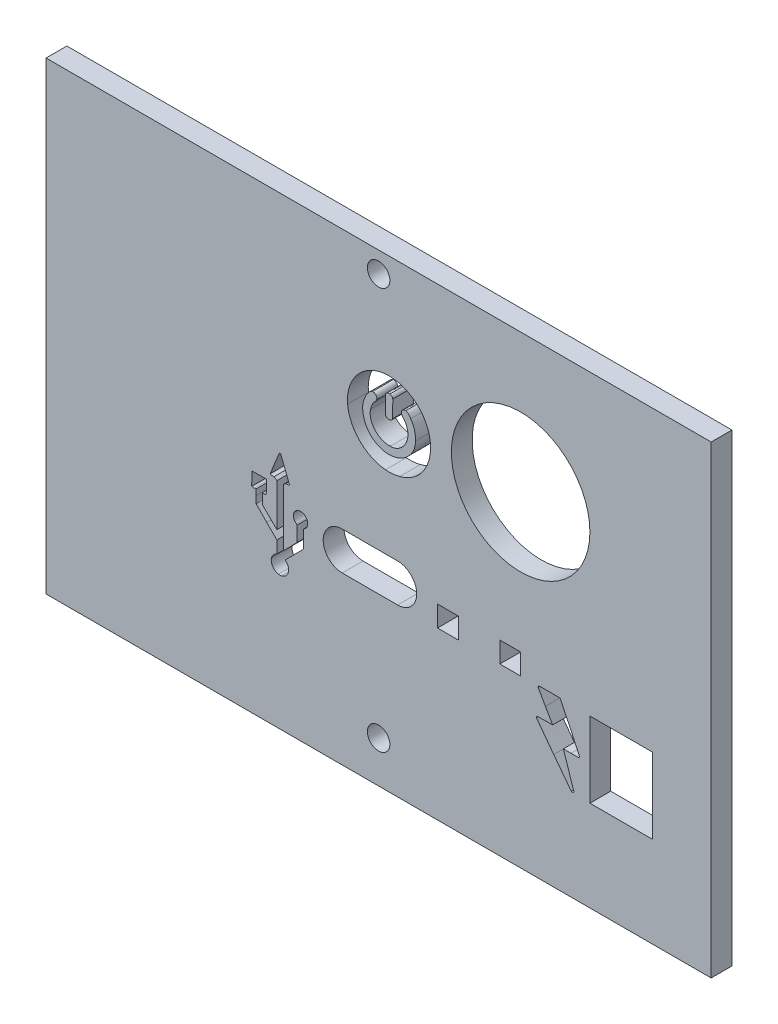
SolidWorks part; units mm, degrees
ref_plane "Alzado" through (0, 0, 0) normal (0, 0, 1) x (1, 0, 0)
ref_plane "Planta" through (0, 0, 0) normal (0, 1, 0) x (1, 0, 0)
ref_plane "Vista lateral" through (0, 0, 0) normal (1, 0, 0) x (0, 0, -1)
sketch "Croquis6" plane through (0, 0, 0) normal (0, 0, 1) x (1, 0, 0)
  line L1 (-48, -33.5) -> (48, -33.5)
  line L2 (-48, -33.5) -> (-48, 33.5)
  line L3 (-48, 33.5) -> (48, 33.5)
  line L4 (48, -33.5) -> (48, 33.5)
  line L5 (-48, -33.5) -> (48, 33.5) construction
  line L6 (-48, 33.5) -> (48, -33.5) construction
  point P0 (0, 0)
  dimension "D1" = 96
  dimension "D2" = 67
extrude "Saliente-Extruir1" add sketch "Croquis6" along normal blind 3
sketch "Croquis7" plane through (0, 0, 0) normal (0, 0, 1) x (1, 0, 0)
  line L5 (48, 33.5) -> (-48, 33.5) construction
  line L13 (-48, -33.5) -> (48, -33.5) construction
  line L14 (30.5, -9.5) -> (39.5, -9.5)
  line L15 (30.5, -9.5) -> (30.5, -20.4)
  line L16 (30.5, -20.4) -> (39.5, -20.4)
  line L17 (39.5, -9.5) -> (39.5, -20.4)
  line L18 (30.5, -9.5) -> (39.5, -20.4) construction
  line L19 (30.5, -20.4) -> (39.5, -9.5) construction
  line L20 (-48, 33.5) -> (-48, -33.5) construction
  line L21 (2.75, -6.75) -> (-5.25, -6.75) construction
  line L22 (2.75, -9.5) -> (-5.25, -9.5)
  line L23 (2.75, -4) -> (-5.25, -4)
  line L24 (48, -33.5) -> (48, 33.5) construction
  line L25 (8.5, -9.5) -> (11.5, -9.5)
  line L26 (8.5, -9.5) -> (8.5, -6.5)
  line L27 (8.5, -6.5) -> (11.5, -6.5)
  line L28 (11.5, -9.5) -> (11.5, -6.5)
  line L29 (8.5, -9.5) -> (11.5, -6.5) construction
  line L30 (8.5, -6.5) -> (11.5, -9.5) construction
  line L32 (17.5, -9.5) -> (20.5, -9.5)
  line L33 (17.5, -9.5) -> (17.5, -6.5)
  line L34 (17.5, -6.5) -> (20.5, -6.5)
  line L35 (20.5, -9.5) -> (20.5, -6.5)
  line L36 (17.5, -9.5) -> (20.5, -6.5) construction
  line L37 (17.5, -6.5) -> (20.5, -9.5) construction
  arc A0 (2.75, -9.5) -> (2.75, -4) centre (2.75, -6.75) ccw
  arc A1 (-5.25, -4) -> (-5.25, -9.5) centre (-5.25, -6.75) ccw
  circle A2 centre (0, -27.5) radius 1.625 construction
  circle A4 centre (0, -27.5) radius 1.625
  circle A5 centre (0, 30.5) radius 1.625
  circle A6 centre (20.5, 13.5) radius 10
  point P12 (35, -14.95)
  point P23 (-1.25, -6.75)
  point P34 (10, -8)
  point P41 (19, -8)
  dimension "D11" = 42.75
  dimension "D12" = 39.5
  dimension "D2" = 20
  dimension "D3" = 27.5
  dimension "D4" = 20
  dimension "D16" = 3.25
  dimension "D17" = 3
  dimension "D18" = 48
  dimension "D5" = 10.9
  dimension "D6" = 9
  dimension "D7" = 24
  dimension "D8" = 87.5
  dimension "D9" = 8
  dimension "D10" = 5.5
  dimension ".5" = 29.5
  dimension "D13" = 24
  dimension "D14" = 3
  dimension "D15" = 6
extrude "Cortar-Extruir1" cut sketch "Croquis7" along normal through all
sketch "Sketch3" plane through (0, 0, 0) normal (0, 0, -1) x (-1, 0, 0)
  line L0 (13.3471, -12.1213) -> (13.4863, -11.9807)
  line L1 (13.4863, -11.9807) -> (12.1786, -10.6698)
  line L2 (10.8062, -7.9977) -> (10.8062, -6.7645)
  line L3 (10.8062, -6.7645) -> (10.695, -6.6943)
  line L4 (11.8656, -6.6758) -> (11.7461, -6.7491)
  line L5 (11.7461, -6.7491) -> (11.7462, -7.8341)
  line L6 (11.7462, -7.8341) -> (11.7463, -8.9191)
  line L7 (11.7463, -8.9191) -> (12.7195, -9.9308)
  line L8 (13.7386, -6.8102) -> (13.7386, -2.6584)
  line L9 (13.7386, -2.6584) -> (13.366, -2.3916)
  line L10 (15.1031, -2.3917) -> (14.6769, -2.6585)
  line L11 (14.6769, -2.6585) -> (14.6769, -5.7252)
  line L12 (14.6769, -5.7252) -> (14.6769, -8.7919)
  line L13 (14.6769, -8.7919) -> (15.7326, -7.7564)
  line L14 (15.7326, -7.7564) -> (16.7882, -6.7209)
  line L15 (16.7882, -6.7209) -> (16.7882, -5.9799)
  line L16 (16.7882, -5.9799) -> (16.7882, -5.239)
  line L17 (16.7882, -5.239) -> (16.5517, -5.239)
  line L18 (16.2018, -4.2113) -> (16.2018, -3.2442)
  line L19 (16.2018, -3.2442) -> (17.2501, -3.2522)
  line L20 (17.2501, -3.2522) -> (18.2984, -3.2602)
  line L21 (18.2984, -3.2602) -> (18.3064, -4.2211)
  line L22 (18.3064, -4.2211) -> (18.3144, -5.1821)
  line L23 (18.3144, -5.1821) -> (18.2388, -5.2108)
  line L24 (17.9452, -5.2395) -> (17.7272, -5.2395)
  line L25 (17.7272, -5.2395) -> (17.7272, -6.0908)
  line L26 (16.1572, -8.6206) -> (14.6775, -10.0831)
  line L27 (14.6775, -10.0831) -> (14.6775, -10.9544)
  line L28 (14.6775, -10.9544) -> (14.6775, -11.8257)
  line L29 (14.6775, -11.8257) -> (14.8112, -11.8907)
  line L30 (14.0062, -14.2401) -> (14.0057, -14.239)
  spline S0 degree 3 poles (14.0057, -14.239) (13.7865, -14.196) (13.5245, -14.0539) (13.3588, -13.8881) knots 0 0 0 0 1 1 1 1
  spline S1 degree 3 poles (13.3588, -13.8881) (12.8723, -13.4016) (12.867, -12.6065) (13.3471, -12.1213) knots 0 0 0 0 1 1 1 1
  spline S2 degree 3 poles (12.1786, -10.6698) (11.4594, -9.9488) (10.8564, -9.3301) (10.8386, -9.2949) knots 0 0 0 0 1 1 1 1
  spline S3 degree 3 poles (10.8386, -9.2949) (10.8165, -9.2512) (10.8062, -8.8393) (10.8062, -7.9977) knots 0 0 0 0 1 1 1 1
  spline S4 degree 3 poles (10.695, -6.6943) (10.4182, -6.5196) (10.238, -6.1959) (10.2359, -5.8694) knots 0 0 0 0 1 1 1 1
  spline S5 degree 3 poles (10.2359, -5.8694) (10.2339, -5.6076) (10.2834, -5.4406) (10.4211, -5.2407) knots 0 0 0 0 1 1 1 1
  spline S6 degree 3 poles (10.4211, -5.2407) (10.849, -4.6193) (11.784, -4.668) (12.1635, -5.3314) knots 0 0 0 0 1 1 1 1
  spline S7 degree 3 poles (12.1635, -5.3314) (12.4235, -5.7858) (12.283, -6.4198) (11.8656, -6.6758) knots 0 0 0 0 1 1 1 1
  spline S8 degree 3 poles (12.7195, -9.9308) (13.2548, -10.4872) (13.7031, -10.9468) (13.7157, -10.9522) knots 0 0 0 0 1 1 1 1
  spline S9 degree 3 poles (13.7157, -10.9522) (13.7283, -10.9572) (13.7386, -9.0937) (13.7386, -6.8102) knots 0 0 0 0 1 1 1 1
  spline S10 degree 3 poles (13.366, -2.3916) (12.9578, -2.3916) (12.8839, -2.3687) (12.8839, -2.2422) knots 0 0 0 0 1 1 1 1
  spline S11 degree 3 poles (12.8839, -2.2422) (12.8839, -2.2029) (13.1643, -1.478) (13.5069, -0.6316) knots 0 0 0 0 1 1 1 1
  spline S12 degree 3 poles (13.5069, -0.6316) (13.8496, 0.2148) (14.1361, 0.9233) (14.1438, 0.9428) knots 0 0 0 0 1 1 1 1
  spline S13 degree 3 poles (14.1438, 0.9428) (14.1658, 0.9995) (14.2718, 1.0203) (14.3144, 0.9762) knots 0 0 0 0 1 1 1 1
  spline S14 degree 3 poles (14.3144, 0.9762) (14.3631, 0.9259) (15.6184, -2.1776) (15.6184, -2.2476) knots 0 0 0 0 1 1 1 1
  spline S15 degree 3 poles (15.6184, -2.2476) (15.6184, -2.3723) (15.5491, -2.3917) (15.1031, -2.3917) knots 0 0 0 0 1 1 1 1
  spline S16 degree 3 poles (16.5517, -5.239) (16.1693, -5.239) (16.2018, -5.3343) (16.2018, -4.2113) knots 0 0 0 0 1 1 1 1
  spline S17 degree 3 poles (18.2388, -5.2108) (18.1972, -5.2266) (18.0651, -5.2395) (17.9452, -5.2395) knots 0 0 0 0 1 1 1 1
  spline S18 degree 3 poles (17.7272, -6.0908) (17.7272, -6.7908) (17.7192, -6.9614) (17.6821, -7.0501) knots 0 0 0 0 1 1 1 1
  spline S19 degree 3 poles (17.6821, -7.0501) (17.6511, -7.1245) (17.1757, -7.614) (16.1572, -8.6206) knots 0 0 0 0 1 1 1 1
  spline S20 degree 3 poles (14.8112, -11.8907) (15.0985, -12.0302) (15.3701, -12.3691) (15.4573, -12.6967) knots 0 0 0 0 1 1 1 1
  spline S21 degree 3 poles (15.4573, -12.6967) (15.641, -13.3866) (15.1812, -14.1075) (14.4716, -14.2421) knots 0 0 0 0 1 1 1 1
  spline S22 degree 3 poles (14.4716, -14.2421) (14.2944, -14.2757) (14.1872, -14.2751) (14.0062, -14.2401) knots 0 0 0 0 1 1 1 1
sketch "Sketch4" plane through (0, 0, 0) normal (0, 0, -1) x (-1, 0, 0)
  line L0 (-27.7842, -15.5148) -> (-28.9122, -15.5148)
  line L1 (-28.9122, -15.5148) -> (-28.9564, -15.4586)
  spline S0 degree 3 poles (-28.3132, -15.5201) (-28.0114, -15.5168) (-27.5175, -15.5168) (-27.2156, -15.5201) knots 0 0 0 0 1 1 1 1
  spline S1 degree 3 poles (-27.2156, -15.5201) (-26.9138, -15.5235) (-27.1607, -15.5262) (-27.7644, -15.5262) knots 0 0 0 0 1 1 1 1
  spline S2 degree 3 poles (-27.7644, -15.5262) (-28.3681, -15.5262) (-28.6151, -15.5235) (-28.3132, -15.5201) knots 0 0 0 0 1 1 1 1
  spline S3 degree 3 poles (-24.5927, -13.3036) (-24.2959, -13.3003) (-23.8164, -13.3003) (-23.5271, -13.3036) knots 0 0 0 0 1 1 1 1
  spline S4 degree 3 poles (-23.5271, -13.3036) (-23.2378, -13.307) (-23.4806, -13.3097) (-24.0667, -13.3097) knots 0 0 0 0 1 1 1 1
  spline S5 degree 3 poles (-24.0667, -13.3097) (-24.6528, -13.3097) (-24.8895, -13.307) (-24.5927, -13.3036) knots 0 0 0 0 1 1 1 1
  spline S6 degree 3 poles (-28.0521, -20.2906) (-28.1292, -20.2578) (-28.1791, -20.1828) (-28.1784, -20.1006) knots 0 0 0 0 1 1 1 1
  spline S7 degree 3 poles (-28.1784, -20.1006) (-28.1781, -20.0552) (-27.8583, -19.0806) (-27.417, -17.7802) knots 0 0 0 0 1 1 1 1
  spline S8 degree 3 poles (-27.417, -17.7802) (-26.9985, -16.5469) (-26.6562, -15.5327) (-26.6562, -15.5264) knots 0 0 0 0 1 1 1 1
  spline S9 degree 3 poles (-26.6562, -15.5264) (-26.6562, -15.52) (-27.1638, -15.5148) (-27.7842, -15.5148) knots 0 0 0 0 1 1 1 1
  spline S10 degree 3 poles (-28.9564, -15.4586) (-28.983, -15.4248) (-29.0003, -15.3718) (-29, -15.3254) knots 0 0 0 0 1 1 1 1
  spline S11 degree 3 poles (-29, -15.3254) (-28.9991, -15.2099) (-26.2859, -9.5165) (-26.2017, -9.4537) knots 0 0 0 0 1 1 1 1
  spline S12 degree 3 poles (-26.2017, -9.4537) (-26.1421, -9.4091) (-26.1287, -9.4087) (-24.6836, -9.403) knots 0 0 0 0 1 1 1 1
  spline S13 degree 3 poles (-24.6836, -9.403) (-23.0998, -9.3967) (-23.1203, -9.3953) (-23.043, -9.5134) knots 0 0 0 0 1 1 1 1
  spline S14 degree 3 poles (-23.043, -9.5134) (-23.0212, -9.5466) (-23.0104, -9.5957) (-23.0155, -9.6377) knots 0 0 0 0 1 1 1 1
  spline S15 degree 3 poles (-23.0155, -9.6377) (-23.0207, -9.6803) (-23.4295, -10.4007) (-24.0728, -11.5011) knots 0 0 0 0 1 1 1 1
  spline S16 degree 3 poles (-24.0728, -11.5011) (-24.6497, -12.4877) (-25.1217, -13.3005) (-25.1217, -13.3073) knots 0 0 0 0 1 1 1 1
  spline S17 degree 3 poles (-25.1217, -13.3073) (-25.1217, -13.3141) (-24.6319, -13.3196) (-24.0333, -13.3196) knots 0 0 0 0 1 1 1 1
  spline S18 degree 3 poles (-24.0333, -13.3196) (-23.2737, -13.3196) (-22.9309, -13.3268) (-22.8984, -13.3434) knots 0 0 0 0 1 1 1 1
  spline S19 degree 3 poles (-22.8984, -13.3434) (-22.8203, -13.3834) (-22.7783, -13.4531) (-22.7779, -13.5434) knots 0 0 0 0 1 1 1 1
  spline S20 degree 3 poles (-22.7779, -13.5434) (-22.7775, -13.6238) (-22.9191, -13.8155) (-25.2724, -16.9214) knots 0 0 0 0 1 1 1 1
  spline S21 degree 3 poles (-25.2724, -16.9214) (-26.6445, -18.7324) (-27.7883, -20.2301) (-27.814, -20.2496) knots 0 0 0 0 1 1 1 1
  spline S22 degree 3 poles (-27.814, -20.2496) (-27.8722, -20.2935) (-27.9954, -20.3148) (-28.0521, -20.2906) knots 0 0 0 0 1 1 1 1
sketch "Sketch5" plane through (0, 0, 0) normal (0, 0, -1) x (-1, 0, 0)
  line L0 (-1.003, 15.9918) -> (-0.984, 13.4574)
  line L1 (-2.0329, 13.4318) -> (-2.0445, 15.8894)
  spline S0 degree 3 poles (-1.5628, 18.5144) (-2.0404, 18.4726) (-2.5013, 18.4548) (-2.9708, 18.3374) knots 0 0 0 0 1 1 1 1
  spline S1 degree 3 poles (-2.9708, 18.3374) (-4.3691, 17.9878) (-5.6316, 17.1291) (-6.4518, 15.9406) knots 0 0 0 0 1 1 1 1
  spline S2 degree 3 poles (-6.4518, 15.9406) (-8.2387, 13.3515) (-7.6893, 9.6933) (-5.1981, 7.7594) knots 0 0 0 0 1 1 1 1
  spline S3 degree 3 poles (-5.1981, 7.7594) (-4.5635, 7.2668) (-3.8217, 6.9121) (-3.0476, 6.7028) knots 0 0 0 0 1 1 1 1
  spline S4 degree 3 poles (-3.0476, 6.7028) (-2.3939, 6.526) (-1.6745, 6.4598) (-0.9996, 6.5241) knots 0 0 0 0 1 1 1 1
  spline S5 degree 3 poles (-0.9996, 6.5241) (1.9, 6.8) (4.1985, 9.0982) (4.4745, 11.9982) knots 0 0 0 0 1 1 1 1
  spline S6 degree 3 poles (4.4745, 11.9982) (4.7363, 14.7492) (2.9572, 17.3525) (0.3572, 18.219) knots 0 0 0 0 1 1 1 1
  spline S7 degree 3 poles (0.3572, 18.219) (-0.2307, 18.4149) (-0.9402, 18.5688) (-1.5628, 18.5144) knots 0 0 0 0 1 1 1 1
  spline S8 degree 3 poles (-1.6396, 16.3162) (-1.3763, 16.3633) (-1.0999, 16.2557) (-1.003, 15.9918) knots 0 0 0 0 1 1 1 1
  spline S9 degree 3 poles (-0.984, 13.4574) (-1.031, 13.2416) (-1.225, 13.0953) (-1.4348, 13.0598) knots 0 0 0 0 1 1 1 1
  spline S10 degree 3 poles (-1.4348, 13.0598) (-1.6876, 13.0169) (-1.9614, 13.1844) (-2.0329, 13.4318) knots 0 0 0 0 1 1 1 1
  spline S11 degree 3 poles (-2.0445, 15.8894) (-2.018, 16.0996) (-1.8485, 16.2788) (-1.6396, 16.3162) knots 0 0 0 0 1 1 1 1
  spline S12 degree 3 poles (-3.918, 15.369) (-3.528, 15.4367) (-3.1755, 15.0388) (-3.3064, 14.6606) knots 0 0 0 0 1 1 1 1
  spline S13 degree 3 poles (-3.3064, 14.6606) (-3.383, 14.4393) (-3.5886, 14.2847) (-3.7204, 14.0974) knots 0 0 0 0 1 1 1 1
  spline S14 degree 3 poles (-3.7204, 14.0974) (-3.9396, 13.7857) (-4.0915, 13.4445) (-4.1769, 13.0734) knots 0 0 0 0 1 1 1 1
  spline S15 degree 3 poles (-4.1769, 13.0734) (-4.5325, 11.5291) (-3.2844, 9.8159) (-1.6652, 9.7966) knots 0 0 0 0 1 1 1 1
  spline S16 degree 3 poles (-1.6652, 9.7966) (0.0439, 9.7763) (1.5187, 11.2636) (1.1649, 13.0222) knots 0 0 0 0 1 1 1 1
  spline S17 degree 3 poles (1.1649, 13.0222) (1.0918, 13.3853) (0.9473, 13.7412) (0.7359, 14.0462) knots 0 0 0 0 1 1 1 1
  spline S18 degree 3 poles (0.7359, 14.0462) (0.5937, 14.2514) (0.3656, 14.4202) (0.2832, 14.6606) knots 0 0 0 0 1 1 1 1
  spline S19 degree 3 poles (0.2832, 14.6606) (0.1535, 15.0388) (0.504, 15.4369) (0.8948, 15.369) knots 0 0 0 0 1 1 1 1
  spline S20 degree 3 poles (0.8948, 15.369) (1.1949, 15.3168) (1.4022, 15.0198) (1.5678, 14.7886) knots 0 0 0 0 1 1 1 1
  spline S21 degree 3 poles (1.5678, 14.7886) (2.0079, 14.1742) (2.3028, 13.4268) (2.3028, 12.6638) knots 0 0 0 0 1 1 1 1
  spline S22 degree 3 poles (2.3028, 12.6638) (2.3029, 10.6471) (0.9193, 8.8974) (-1.1532, 8.7001) knots 0 0 0 0 1 1 1 1
  spline S23 degree 3 poles (-1.1532, 8.7001) (-3.2001, 8.5052) (-5.3226, 10.1388) (-5.3261, 12.2798) knots 0 0 0 0 1 1 1 1
  spline S24 degree 3 poles (-5.3261, 12.2798) (-5.3275, 13.1692) (-5.1655, 14.001) (-4.631, 14.7374) knots 0 0 0 0 1 1 1 1
  spline S25 degree 3 poles (-4.631, 14.7374) (-4.4539, 14.9814) (-4.2379, 15.3134) (-3.918, 15.369) knots 0 0 0 0 1 1 1 1
extrude "Cortar-Extruir3" cut sketch "Sketch5" against normal blind 10
extrude "Cortar-Extruir4" cut sketch "Sketch3" against normal up to next (3 mm away)
extrude "Cortar-Extruir5" cut sketch "Sketch4" against normal up to next (3 mm away)
